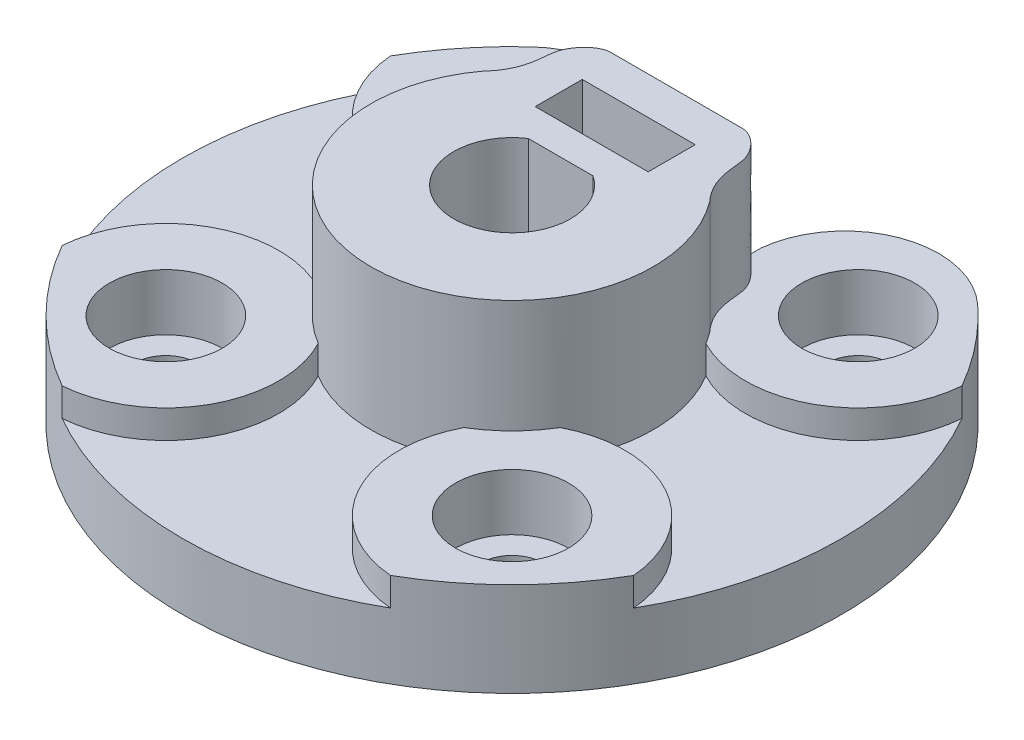
SolidWorks part; units mm, degrees
material "ABS"
ref_plane "Спереди" through (0, 0, 0) normal (0, 0, 1) x (1, 0, 0)
ref_plane "Сверху" through (0, 0, 0) normal (0, 1, 0) x (1, 0, 0)
ref_plane "Справа" through (0, 0, 0) normal (1, 0, 0) x (0, 0, -1)
sketch "Эскиз1" plane through (0, 0, 0) normal (0, 1, 0) x (1, 0, 0)
  circle A0 centre (0, 0) radius 17.5
  dimension "D1" = 35
extrude "Бобышка-Вытянуть1" add sketch "Эскиз1" along normal blind 2
sketch "Эскиз2" plane through (0, 2, 0) normal (0, 1, 0) x (1, 0, 0)
  line L0 (-1.7634, 2.73) -> (1.7634, 2.73)
  circle A0 centre (0, 0) radius 8.75
  arc A1 (-1.7634, 2.73) -> (1.7634, 2.73) centre (0, 0) ccw
  dimension "D1" = 3.25
  dimension "D2" = 17.5
  dimension "D3" = 2.73
extrude "Бобышка-Вытянуть2" add sketch "Эскиз2" along normal blind 9
sketch "Эскиз12" plane through (0, 2, 0) normal (0, 1, 0) x (1, 0, 0)
  line L0 (-1.7634, 2.73) -> (1.7634, 2.73)
  arc A0 (-1.7634, 2.73) -> (1.7634, 2.73) centre (0, 0) ccw
extrude "Вырез-Вытянуть8" cut sketch "Эскиз12" against normal up to surface (2 mm away) up to face at (0, 0, 17.5)
sketch "Эскиз9" plane through (0, 2, 0) normal (0, 1, 0) x (1, 0, 0)
  line L0 (0, 0) -> (12.3744, 12.3744) construction
  line L1 (12.3744, 12.3744) -> (-12.3744, -12.3744) construction
  circle A0 centre (0, 0) radius 17.5 construction
  circle A1 centre (9.1924, 9.1924) radius 1.65
  dimension "D1" = 3.3
  dimension "D2" = 13
extrude "Вырез-Вытянуть7" cut sketch "Эскиз9" against normal through all
ref_axis "Ось3" through (0, 0, 0) along (0, 1, 0)
pattern_circular "Круговой массив2" count 4 over 360 about axis through (0, 0, 0) along (0, 1, 0) of "Вырез-Вытянуть7"
sketch "Эскиз10" plane through (0, 2, 0) normal (0, 1, 0) x (1, 0, 0)
  circle A0 centre (0, 0) radius 17.5
  circle A1 centre (0, 0) radius 8.75
  circle A2 centre (-9.1924, 9.1924) radius 3
  circle A3 centre (9.1924, 9.1924) radius 3
  circle A4 centre (9.1924, -9.1924) radius 3
  circle A5 centre (-9.1924, -9.1924) radius 3
  point P17 (0, 0)
  dimension "D2" = 6
  dimension "D1" = 4
extrude "Бобышка-Вытянуть3" add sketch "Эскиз10" along normal blind 3
ref_plane "Плоскость1" through (0, 0, -8.75) normal (0, 0, -1) x (-1, 0, 0)
sketch "Эскиз14" plane through (0, 0, -8.75) normal (0, 0, -1) x (-1, 0, 0)
  line L0 (-17.5, 0) -> (17.5, 0) construction
  line L1 (-3.5, 0) -> (3.5, 0)
  line L2 (-3.5, 0) -> (-3.5, 5)
  line L3 (-3.5, 5) -> (3.5, 5)
  line L4 (3.5, 0) -> (3.5, 5)
  line L6 (17.5, 5) -> (-17.5, 5) construction
  point P8 (0, 5)
  dimension "D1" = 7
extrude "Вырез-Вытянуть9" cut sketch "Эскиз14" along normal through all
sketch "Эскиз3" plane through (0, 0, -2.73) normal (0, 0, 1) x (1, 0, 0)
  line L1 (17.5, 5) -> (-17.5, 5) construction
  circle A0 centre (0, 6) radius 1.625
  dimension "D2" = 3.25
  dimension "D1" = 1
extrude "Вырез-Вытянуть1" cut sketch "Эскиз3" against normal through all
sketch "Эскиз4" plane through (0, 11, 0) normal (0, 1, 0) x (1, 0, 0)
  line L0 (1.7634, 2.73) -> (-1.7634, 2.73) construction
  line L1 (-3, 6.73) -> (3, 6.73)
  line L2 (-3, 6.73) -> (-3, 4.23)
  line L3 (-3, 4.23) -> (3, 4.23)
  line L4 (3, 6.73) -> (3, 4.23)
  line L5 (-3, 6.73) -> (3, 4.23) construction
  line L6 (-3, 4.23) -> (3, 6.73) construction
  point P0 (0, 5.48)
  point P5 (0, 2.73)
  dimension "D1" = 1.5
  dimension "D2" = 2.5
  dimension "D3" = 6
extrude "Вырез-Вытянуть2" cut sketch "Эскиз4" against normal through all
sketch "Эскиз11" plane through (0, 0, -6.73) normal (0, 0, 1) x (1, 0, 0)
  line L0 (3, 11) -> (-3, 11) construction
  line L1 (5, 1) -> (3.5, 1)
  line L2 (5, 1) -> (5, 11)
  line L3 (5, 11) -> (-5, 11)
  line L4 (-5, 1) -> (-5, 11)
  line L5 (5, 1) -> (-5, 11) construction
  line L6 (5, 11) -> (-5, 1) construction
  line L7 (-17.5, 0) -> (17.5, 0) construction
  line L9 (3.5, 1) -> (3.5, 0)
  line L10 (3.5, 0) -> (-3.5, 0)
  line L11 (-3.5, 1) -> (-3.5, 0)
  line L12 (3.5, 5) -> (3.5, 0) construction
  line L13 (-3.5, 0) -> (-3.5, 5) construction
  line L14 (-3.5, 1) -> (-5, 1)
  circle A0 centre (0, 6) radius 1.625
  point P0 (0, 6)
  dimension "D1" = 2
extrude "Бобышка-Вытянуть4" add sketch "Эскиз11" against normal blind 3
fillet "Скругление2" radius 5 2 edges at (3.5, 2.5, -17.1464) (-3.5, 2.5, -17.1464)
sketch "Эскиз16" plane through (0, 11, 0) normal (0, 1, 0) x (1, 0, 0)
  line L0 (0, 0) -> (0, 9.73) construction
  line L1 (5, 9.73) -> (-5, 9.73) construction
  line L2 (-6, 4.5) -> (-6, 6.3689) construction
  line L3 (-6, 4.5) -> (-5, 7.1807)
  line L4 (6, 4.5) -> (6, 6.3689) construction
  line L5 (6, 4.5) -> (5, 7.1807)
  arc A0 (-5, 7.1807) -> (5, 7.1807) centre (0, 0) ccw
  arc A1 (-5, 7.1807) -> (5, 7.1807) centre (0, 0) ccw construction
  arc A2 (-6, 4.5) -> (6, 4.5) centre (0, 0) ccw
  dimension "D1" = 6
  dimension "D2" = 7.5
extrude "Вырез-Вытянуть11" cut sketch "Эскиз16" against normal up to surface (6 mm away) up to face at (0, 5, -4.7333)
sketch "Эскиз17" plane through (0, 5, 0) normal (0, 1, 0) x (1, 0, 0)
  arc A0 (-15.1736, 8.7184) -> (-15.1736, -8.7184) centre (0, 0) ccw
  arc A1 (-11.8594, 12.8688) -> (11.8594, 12.8688) centre (0, 0) ccw construction
  arc A2 (-8.7184, -15.1736) -> (8.7184, -15.1736) centre (0, 0) ccw
  arc A3 (15.1736, -8.7184) -> (15.1736, 8.7184) centre (0, 0) ccw
  arc A4 (-6.4253, 3.8686) -> (-6.4253, -3.8686) centre (0, 0) ccw
  arc A5 (-15.1736, 8.7184) -> (-6.4253, 3.8686) centre (-9.1924, 9.1924) ccw
  arc A6 (-6.4253, -3.8686) -> (-15.1736, -8.7184) centre (-9.1924, -9.1924) ccw
  arc A7 (-3.8686, -6.4253) -> (-8.7184, -15.1736) centre (-9.1924, -9.1924) cw
  arc A8 (3.8686, -6.4253) -> (8.7184, -15.1736) centre (9.1924, -9.1924) ccw
  arc A9 (6.4253, -3.8686) -> (15.1736, -8.7184) centre (9.1924, -9.1924) cw
  arc A10 (15.1736, 8.7184) -> (6.4253, 3.8686) centre (9.1924, 9.1924) cw
  arc A11 (-3.8686, -6.4253) -> (3.8686, -6.4253) centre (0, 0) ccw
  arc A12 (6.4253, -3.8686) -> (6.4253, 3.8686) centre (0, 0) ccw
  arc A13 (-6, 4.5) -> (6, 4.5) centre (0, 0) ccw construction
  dimension "D1" = 6
extrude "Вырез-Вытянуть12" cut sketch "Эскиз17" against normal blind 1.5
sketch "Эскиз18" plane through (0, 11, 0) normal (0, 1, 0) x (1, 0, 0)
  line L0 (-1.7634, 2.73) -> (1.7634, 2.73)
  line L1 (-1.7186, 2.58) -> (1.7186, 2.58)
  arc A1 (-1.7634, 2.73) -> (1.7634, 2.73) centre (0, 0) ccw
  arc A2 (-1.7186, 2.58) -> (1.7186, 2.58) centre (0, 0) ccw
  point P11 (0, 2.58)
  point P12 (0, -3.1)
  dimension "D1" = 3.25
  dimension "D3" = 3.1
  dimension "D2" = 0.15
  dimension "D4" = 5.68
extrude "Бобышка-Вытянуть5" add sketch "Эскиз18" against normal through all
sketch "Эскиз19" plane through (0, 0, -9.73) normal (0, 0, -1) x (-1, 0, 0)
  line L0 (-5, 11) -> (5, 11)
  line L1 (5, 11) -> (5, 5)
  line L2 (5, 5) -> (3.5, 5)
  line L3 (3.5, 5) -> (3.5, 0)
  line L4 (3.5, 0) -> (-3.5, 0)
  line L5 (-3.5, 0) -> (-3.5, 5)
  line L6 (-3.5, 5) -> (-5, 5)
  line L7 (-5, 5) -> (-5, 11)
  circle A0 centre (0, 6) radius 1.625
  circle A1 centre (0, 6) radius 1.625 construction
extrude "Вырез-Вытянуть13" cut sketch "Эскиз19" against normal blind 1
sketch "Эскиз20" plane through (0, 11, 0) normal (0, 1, 0) x (1, 0, 0)
  line L0 (-5, 7.1807) -> (-3.5, 8.73) construction
  line L1 (-3.5, 8.73) -> (-5, 8.73)
  line L2 (-5, 8.73) -> (-5, 7.1807)
  line L3 (0, 6.73) -> (0, 8.73) construction
  line L4 (3, 6.73) -> (-3, 6.73) construction
  line L5 (-5, 8.73) -> (5, 8.73) construction
  line L6 (-5, 7.1807) -> (-6, 4.5)
  line L7 (5, 7.1807) -> (3.5, 8.73) construction
  line L8 (5, 7.1807) -> (6, 4.5)
  line L9 (5, 8.73) -> (5, 7.1807)
  line L10 (3.5, 8.73) -> (5, 8.73)
  spline S0 degree 3 poles (-3.5, 8.73) (-4.0797, 8.73) (-4.926, 7.8827) (-5.0906, 6.4001) (-5.1608, 5.406) (-6, 4.5) knots 0 0 0 0 0.430033 0.530033 1 1 1 1
  spline S1 degree 3 poles (3.5, 8.73) (4.0797, 8.73) (4.926, 7.8827) (5.0906, 6.4001) (5.1608, 5.406) (6, 4.5) knots 0 0 0 0 0.430033 0.530033 1 1 1 1
  line M1 (5, 8.73) -> (-5, 8.73)
  line M2 (-5, 8.73) -> (-5, 7.1807)
  line M3 (-5, 7.1807) -> (-6, 4.5)
  line M5 (6, 4.5) -> (5, 7.1807)
  line M6 (5, 7.1807) -> (5, 8.73)
extrude "Вырез-Вытянуть15" cut sketch "Эскиз20" against normal up to surface (6 mm away) contours S0 M1 M2 | S0 M3 | S1 M1 M6 | S1 M5 | L8 S1 L10 L9 region at (-4.6324, 11, -8.3254) region at (-5.4202, 11, -5.7425) region at (5.4202, 11, -5.7425) region at (4.6324, 11, -8.3254) up to face at (9.1924, 5, 12.1924)
sketch "Эскиз22" plane through (0, 3.5, 0) normal (0, 1, 0) x (1, 0, 0)
  line L0 (-15.1736, 8.7184) -> (-15.1736, -8.7184)
  line L1 (-8.7184, -15.1736) -> (8.7184, -15.1736)
  line L2 (15.1736, 8.7184) -> (15.1736, -8.7184)
  arc A0 (15.1736, 8.7184) -> (15.1736, -8.7184) centre (0, 0) cw
  arc A1 (8.7184, -15.1736) -> (-8.7184, -15.1736) centre (0, 0) cw
  arc A2 (-15.1736, -8.7184) -> (-8.7184, -15.1736) centre (0, 0) ccw construction
  arc A3 (-15.1736, -8.7184) -> (-15.1736, 8.7184) centre (0, 0) cw
  arc M3 (-8.7184, -15.1736) -> (8.7184, -15.1736) centre (0, 0) ccw
extrude "Вырез-Вытянуть16" [suppressed] cut sketch "Эскиз22" against normal through all contours A3 L0 | L1 M3 | A0 L2
